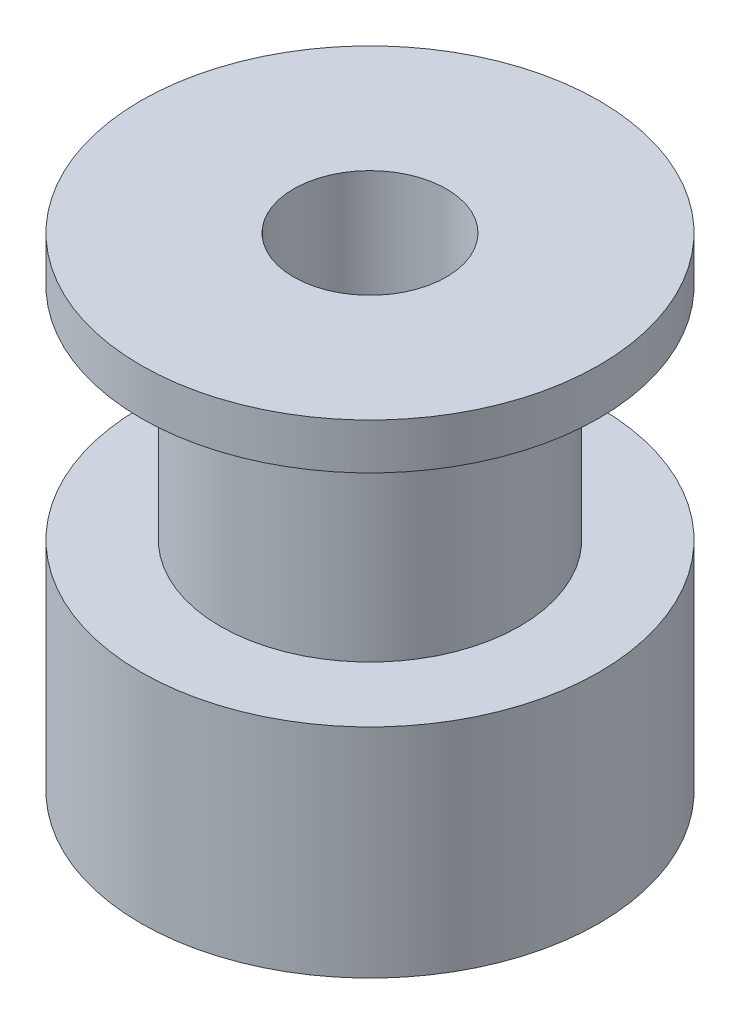
SolidWorks part; units mm, degrees
ref_plane "Front Plane" through (0, 0, 0) normal (0, 0, 1) x (1, 0, 0)
ref_plane "Top Plane" through (0, 0, 0) normal (0, 1, 0) x (1, 0, 0)
ref_plane "Right Plane" through (0, 0, 0) normal (1, 0, 0) x (0, 0, -1)
sketch "Sketch1" plane through (0, 0, 0) normal (0, 1, 0) x (1, 0, 0)
  circle A0 centre (0, 0) radius 7.5
  dimension "D1" = 15
extrude "Boss-Extrude1" add sketch "Sketch1" along normal blind 7.12
sketch "Sketch2" plane through (0, 7.12, 0) normal (0, 1, 0) x (1, 0, 0)
  circle A0 centre (0, 0) radius 4.9
  dimension "D1" = 9.8
extrude "Boss-Extrude2" add sketch "Sketch2" along normal blind 7.2
sketch "Sketch3" plane through (0, 14.32, 0) normal (0, 1, 0) x (1, 0, 0)
  circle A0 centre (0, 0) radius 7.5
extrude "Boss-Extrude3" add sketch "Sketch3" along normal blind 1.5
sketch "Sketch4" plane through (0, 15.82, 0) normal (0, 1, 0) x (1, 0, 0)
  circle A0 centre (0, 0) radius 2.5
  dimension "D1" = 5
extrude "Cut-Extrude1" cut sketch "Sketch4" against normal through all
